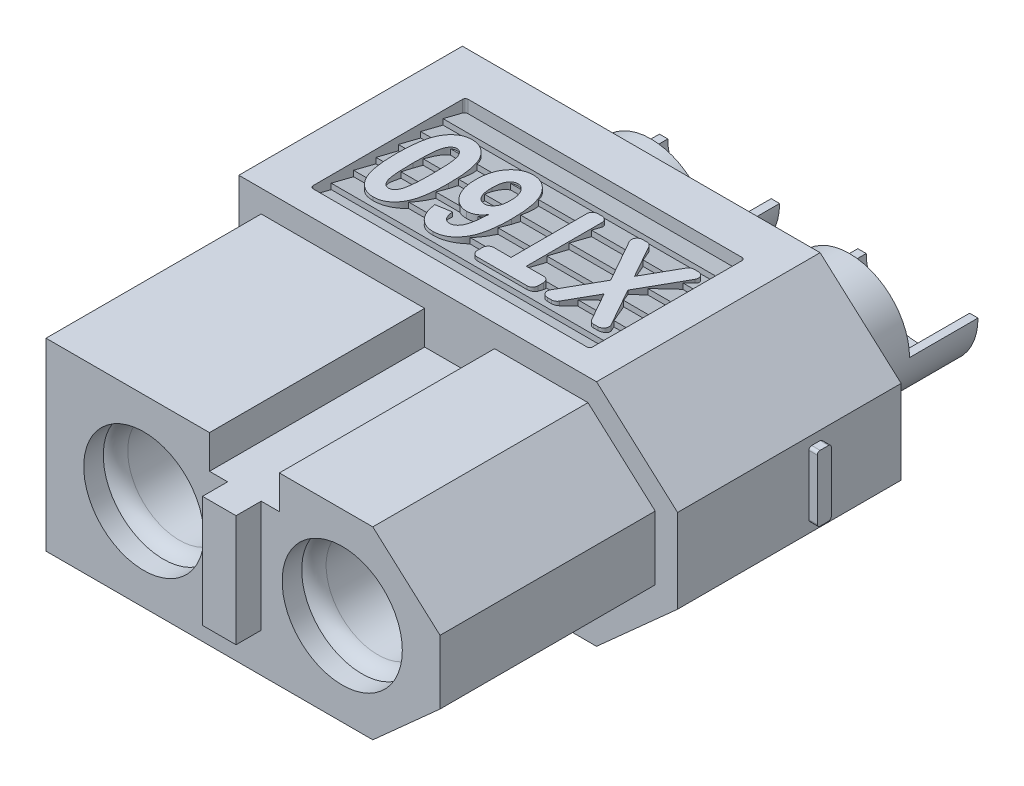
SolidWorks part; units mm, degrees
material "Nylon 101"
ref_plane "Plano frontal" through (0, 0, 0) normal (0, 0, 1) x (1, 0, 0)
ref_plane "Plano superior" through (0, 0, 0) normal (0, 1, 0) x (1, 0, 0)
ref_plane "Plano direito" through (0, 0, 0) normal (1, 0, 0) x (0, 0, -1)
sketch "Esboço1" plane through (0, 0, 0) normal (0, 0, 1) x (1, 0, 0)
  line L0 (0, 0) -> (12.8, 0)
  line L1 (12.8, 0) -> (15.7, 2.6)
  line L2 (15.7, 2.6) -> (15.7, 5.6)
  line L3 (15.7, 5.6) -> (12.8, 8.2)
  line L4 (12.8, 8.2) -> (0, 8.2)
  line L5 (0, 8.2) -> (0, 0)
  dimension "D1" = 12.8
  dimension "D2" = 3
  dimension "D3" = 15.7
  dimension "D4" = 8.2
extrude "Ressalto-extrusão1" add sketch "Esboço1" along normal blind 16.2
sketch "Esboço2" plane through (0, 0, 16.2) normal (0, 0, 1) x (1, 0, 0)
  line L0 (0.75, 7.45) -> (0.75, 0.75)
  line L1 (0.75, 0.75) -> (12.513, 0.75)
  line L2 (12.513, 0.75) -> (14.95, 2.9349)
  line L3 (14.95, 2.9349) -> (14.95, 5.2651)
  line L4 (14.95, 5.2651) -> (12.513, 7.45)
  line L5 (12.513, 7.45) -> (0.75, 7.45)
  line L6 (0, 8.2) -> (0, 0)
  line L7 (0, 0) -> (12.8, 0)
  line L8 (12.8, 0) -> (15.7, 2.6)
  line L9 (15.7, 2.6) -> (15.7, 5.6)
  line L10 (15.7, 5.6) -> (12.8, 8.2)
  line L11 (12.8, 8.2) -> (0, 8.2)
  line L12 (0, 8.2) -> (0, 0) construction
  line L13 (0, 0) -> (12.8, 0) construction
  line L14 (12.8, 0) -> (15.7, 2.6) construction
  line L15 (15.7, 2.6) -> (15.7, 5.6) construction
  line L16 (15.7, 5.6) -> (12.8, 8.2) construction
  line L17 (12.8, 8.2) -> (0, 8.2) construction
  dimension "D1" = 0
  dimension "D2" = 0.75
extrude "Corte-extrusão1" cut sketch "Esboço2" against normal blind 9.4
sketch "Esboço3" plane through (0, 0, 6.8) normal (0, 0, 1) x (1, 0, 0)
  line L1 (7.1, 1.66) -> (8.7, 1.66)
  line L2 (7.1, 1.66) -> (7.1, 0.75)
  line L3 (7.1, 0.75) -> (8.7, 0.75)
  line L4 (8.7, 1.66) -> (8.7, 0.75)
  line L7 (0.75, 0.75) -> (12.513, 0.75) construction
  line L8 (0, 0) -> (12.8, 0) construction
  line L9 (0, 8.2) -> (0, 0) construction
  dimension "D1" = 1.6
  dimension "D2" = 1.66
  dimension "D3" = 8.7
extrude "Ressalto-extrusão2" add sketch "Esboço3" along normal blind 8
sketch "Esboço4" plane through (0, 0, 6.8) normal (0, 0, 1) x (1, 0, 0)
  line L0 (12.513, 7.45) -> (0.75, 7.45) construction
  line L1 (8.7, 1.75) -> (7.1, 1.75)
  line L2 (8.7, 1.75) -> (8.7, 6.45)
  line L3 (8.7, 6.45) -> (7.1, 6.45)
  line L4 (7.1, 1.75) -> (7.1, 6.45)
  line L5 (0.75, 0.75) -> (7.1, 0.75) construction
  line L7 (7.1, 1.66) -> (7.1, 0.75) construction
  line L8 (8.7, 0.75) -> (8.7, 1.66) construction
  dimension "D1" = 1
  dimension "D2" = 1
extrude "Corte-extrusão2" cut sketch "Esboço4" against normal blind 1.5
sketch "Esboço5" plane through (0, 0, 0) normal (0, 0, -1) x (-1, 0, 0)
  line L0 (-15.7, 2.6) -> (-15.7, 5.6) construction
  line L3 (0, 8.2) -> (0, 0) construction
  circle A0 centre (-11.35, 4.1) radius 3
  circle A1 centre (-4.25, 4.1) radius 3
  point P6 (-15.7, 4.1)
  point P9 (-15.7, 4.1)
  dimension "D1" = 6
  dimension "D3" = 4.25
  dimension "D2" = 4.35
extrude "Corte-extrusão3" cut sketch "Esboço5" against normal blind 2
sketch "Esboço6" plane through (0, 0, 2) normal (0, 0, -1) x (-1, 0, 0)
  line L0 (-15.7, 2.6) -> (-15.7, 5.6) construction
  line L3 (0, 8.2) -> (0, 0) construction
  circle A0 centre (-11.35, 4.1) radius 2.15
  circle A2 centre (-4.25, 4.1) radius 2.15
  point P4 (-15.7, 4.1)
  dimension "D1" = 4.3
  dimension "D2" = 6.5
  dimension "D3" = 6.4
extrude "Corte-extrusão4" cut sketch "Esboço6" against normal through all
sketch "Esboço7" plane through (0, 0, 0) normal (-1, 0, 0) x (0, 0, 1)
  line L0 (2.8, 4.35) -> (2.05, 4.35)
  line L1 (4.25, 4.35) -> (3.5, 4.35)
  line L2 (4.35, 4.25) -> (4.35, 3.95)
  line L3 (4.25, 3.85) -> (3.5, 3.85)
  line L4 (1.95, 4.25) -> (1.95, 3.95)
  line L5 (3.3, 5.3) -> (3, 5.3)
  line L6 (3.4, 5.2) -> (3.4, 4.45)
  line L7 (3.3, 2.9) -> (3, 2.9)
  line L8 (2.9, 5.2) -> (2.9, 4.45)
  line L9 (2.8, 3.85) -> (2.05, 3.85)
  line L10 (3.4, 3.75) -> (3.4, 3)
  line L11 (2.9, 3.75) -> (2.9, 3)
  line L12 (0, 8.2) -> (0, 0) construction
  arc A0 (3, 2.9) -> (2.9, 3) centre (3, 3) cw
  arc A1 (3.3, 5.3) -> (3.4, 5.2) centre (3.3, 5.2) cw
  arc A2 (3, 5.3) -> (2.9, 5.2) centre (3, 5.2) ccw
  arc A3 (2.05, 4.35) -> (1.95, 4.25) centre (2.05, 4.25) ccw
  arc A4 (2.05, 3.85) -> (1.95, 3.95) centre (2.05, 3.95) cw
  arc A5 (2.8, 3.85) -> (2.9, 3.75) centre (2.8, 3.75) cw
  arc A6 (2.8, 4.35) -> (2.9, 4.45) centre (2.8, 4.45) ccw
  arc A7 (3.5, 3.85) -> (3.4, 3.75) centre (3.5, 3.75) ccw
  arc A8 (3.4, 3) -> (3.3, 2.9) centre (3.3, 3) cw
  arc A9 (4.35, 3.95) -> (4.25, 3.85) centre (4.25, 3.95) cw
  arc A10 (4.25, 4.35) -> (4.35, 4.25) centre (4.25, 4.25) cw
  arc A11 (3.5, 4.35) -> (3.4, 4.45) centre (3.5, 4.45) cw
  point P12 (1.95, 4.1)
  point P15 (0, 4.1)
  point P28 (2.9, 3.85)
  point P33 (3.4, 3.85)
  point P38 (4.35, 3.85)
  point P41 (4.35, 4.35)
  dimension "D4" = 0.1
  dimension "D1" = 2.4
  dimension "D2" = 0.5
  dimension "D3" = 4.35
extrude "Ressalto-extrusão3" add sketch "Esboço7" along normal blind 0.3
sketch "Esboço8" plane through (15.7, 0, 0) normal (1, 0, 0) x (0, 0, -1)
  line L0 (0, 2.6) -> (0, 5.6) construction
  line L1 (-3.2, 2.925) -> (-2.9, 2.925)
  line L2 (-3.3, 3.025) -> (-3.3, 5.175)
  line L3 (-3.2, 5.275) -> (-2.9, 5.275)
  line L4 (-2.8, 3.025) -> (-2.8, 5.175)
  arc A0 (-3.3, 5.175) -> (-3.2, 5.275) centre (-3.2, 5.175) cw
  arc A1 (-2.9, 5.275) -> (-2.8, 5.175) centre (-2.9, 5.175) cw
  arc A2 (-3.2, 2.925) -> (-3.3, 3.025) centre (-3.2, 3.025) cw
  arc A3 (-2.9, 2.925) -> (-2.8, 3.025) centre (-2.9, 3.025) ccw
  point P4 (-2.8, 4.1)
  point P7 (0, 4.1)
  point P10 (-3.3, 5.275)
  point P13 (-2.8, 5.275)
  point P18 (-2.8, 2.925)
  dimension "D4" = 0.1
  dimension "D1" = 2.35
  dimension "D2" = 0.5
  dimension "D3" = 3.3
extrude "Ressalto-extrusão4" add sketch "Esboço8" along normal blind 0.3
sketch "Esboço9" plane through (0, 0, 0) normal (0, -1, 0) x (1, 0, 0)
  line L0 (12.8, 16.2) -> (12.8, 0) construction
  line L1 (1.75, 7.0931) -> (11.55, 7.0931)
  line L2 (1.65, 6.9931) -> (1.65, 1.6431)
  line L3 (1.75, 1.5431) -> (11.55, 1.5431)
  line L4 (11.65, 6.9931) -> (11.65, 1.6431)
  arc A0 (1.65, 1.6431) -> (1.75, 1.5431) centre (1.75, 1.6431) ccw
  arc A1 (11.55, 1.5431) -> (11.65, 1.6431) centre (11.55, 1.6431) ccw
  arc A2 (11.55, 7.0931) -> (11.65, 6.9931) centre (11.55, 6.9931) cw
  arc A3 (1.75, 7.0931) -> (1.65, 6.9931) centre (1.75, 6.9931) ccw
  dimension "D1" = 0.1
  dimension "D2" = 1.15
  dimension "D3" = 10
  dimension "D4" = 5.55
extrude "Corte-extrusão5" cut sketch "Esboço9" against normal blind 0.75
sketch "Esboço10" plane through (1.65, 0, 0) normal (1, 0, 0) x (0, 0, -1)
  line L0 (-6.8, 0.75) -> (-1.6431, 0.75) construction
  line L1 (-1.5431, 0.75) -> (-1.5431, 0) construction
  line L2 (-3.1431, 0.25) -> (-2.3431, 0.45)
  line L3 (-2.3431, 0.45) -> (-2.3431, 0.25)
  line L5 (-3.1431, 0.45) -> (-3.1431, 0.25)
  line L6 (-2.3431, 0.45) -> (-2.3431, 0.25)
  line L7 (-3.9431, 0.25) -> (-3.1431, 0.45)
  line L8 (-3.9431, 0.45) -> (-3.9431, 0.25)
  line L9 (-4.7431, 0.25) -> (-3.9431, 0.45)
  line L10 (-4.7431, 0.45) -> (-4.7431, 0.25)
  line L11 (-5.5431, 0.25) -> (-4.7431, 0.45)
  line L12 (-5.5431, 0.45) -> (-5.5431, 0.25)
  line L13 (-6.3431, 0.25) -> (-5.5431, 0.45)
  line L14 (-6.3431, 0.45) -> (-6.3431, 0.25)
  line L15 (-7.1431, 0.25) -> (-6.3431, 0.45)
  line L16 (-7.1431, 0.45) -> (-7.1431, 0.25)
  line L17 (-7.1431, 0.45) -> (-7.1431, 0.75)
  line L19 (-2.3431, 0.25) -> (-1.5431, 0.45)
  line L20 (-7.1431, 0.75) -> (-1.5431, 0.75)
  line L21 (-1.5431, 0.45) -> (-1.5431, 0.75)
  line L31 (-2.3431, 0.25) -> (-1.5431, 0.45)
  dimension "D1" = 0.8
  dimension "D2" = 0.2
  dimension "D3" = 0.3
  dimension "D4" = 7
extrude "Ressalto-extrusão7" add sketch "Esboço10" along normal up to surface (10 mm away) up to face at (11.65, 0.45, 4.8145)
ref_plane "Plano1" through (0, 4.1, 0) normal (0, 1, 0) x (1, 0, 0)
mirror "Espelhar1" about plane through (0, 4.1, 0) normal (0, 1, 0) of "Corte-extrusão5", "Ressalto-extrusão7"
ref_plane "Plano2" through (0, 0.5, 0) normal (0, -1, 0) x (-1, 0, 0)
sketch "Esboço11" plane through (0, 0.5, 0) normal (0, -1, 0) x (-1, 0, 0)
  line L1 (-2.131, -7.0931) -> (-2.131, -1.5431) construction
  line L2 (-11.55, -7.0931) -> (-1.75, -7.0931) construction
  line L3 (-11.55, -1.5431) -> (-1.75, -1.5431) construction
  line L4 (-0.85, -6.1831) -> (-0.85, -2.4531) construction
  line L5 (-0.85, -2.4531) -> (-11.65, -2.4531) construction
  line L8 (-11.65, -3.1431) -> (-11.65, -2.3431) construction
  line L10 (-1.65, -6.9931) -> (-1.65, -1.6431) construction
  text T0 "<b><i>TGY</i></b>" font "Calibri" height in points 14
  point P8 (-0.85, -4.3181)
  point P9 (-2.131, -4.3181)
  dimension "D2" = 0.8
  dimension "D1" = 3.73
extrude "Ressalto-extrusão8" add sketch "Esboço11" along normal blind 0.3
ref_plane "Plano3" through (0, 7.7, 0) normal (0, 1, 0) x (1, 0, 0)
sketch "Esboço12" plane through (0, 7.7, 0) normal (0, 1, 0) x (1, 0, 0)
  line L0 (11.0942, -7.0931) -> (11.0942, -1.5431) construction
  line L1 (11.55, -7.0931) -> (1.75, -7.0931) construction
  line L3 (11.3535, -6.0681) -> (11.3535, -2.5681) construction
  line L6 (11.3535, -2.5681) -> (1.9746, -2.5681) construction
  line L7 (11.185, -2.8665) -> (10.3201, -4.3984)
  line L8 (10.3201, -4.3984) -> (11.0942, -5.7698)
  line L9 (10.92, -6.0681) -> (10.7649, -6.0681)
  line L10 (10.5908, -5.9665) -> (10.0126, -4.9431)
  line L11 (10.0126, -4.9431) -> (9.435, -5.9664)
  line L12 (9.2609, -6.0681) -> (9.1051, -6.0681)
  line L13 (8.931, -5.7698) -> (9.705, -4.3984)
  line L14 (9.705, -4.3984) -> (8.8401, -2.8665)
  line L15 (9.0143, -2.5681) -> (9.1699, -2.5681)
  line L16 (9.3441, -2.6698) -> (10.0126, -3.8543)
  line L17 (10.0126, -3.8543) -> (10.6817, -2.6698)
  line L18 (10.8559, -2.5681) -> (11.0109, -2.5681)
  line L19 (7.7626, -2.7681) -> (7.7626, -5.4772)
  line L20 (7.7626, -5.4772) -> (8.3808, -5.4772)
  line L21 (8.5808, -5.6772) -> (8.5808, -5.8681)
  line L22 (8.3808, -6.0681) -> (6.5989, -6.0681)
  line L23 (6.3989, -5.8681) -> (6.3989, -5.6772)
  line L24 (6.5989, -5.4772) -> (7.2171, -5.4772)
  line L25 (7.2171, -5.4772) -> (7.2171, -2.7681)
  line L26 (7.4171, -2.5681) -> (7.5626, -2.5681)
  line L27 (4.2171, -5.2045) -> (4.7626, -5.1136)
  line L28 (11.55, -1.5431) -> (1.75, -1.5431) construction
  arc A0 (7.2171, -2.7681) -> (7.4171, -2.5681) centre (7.4171, -2.7681) cw
  arc A1 (7.7626, -2.7681) -> (7.5626, -2.5681) centre (7.5626, -2.7681) ccw
  arc A2 (6.3989, -5.6772) -> (6.5989, -5.4772) centre (6.5989, -5.6772) cw
  arc A3 (6.5989, -6.0681) -> (6.3989, -5.8681) centre (6.5989, -5.8681) cw
  arc A4 (8.5808, -5.8681) -> (8.3808, -6.0681) centre (8.3808, -5.8681) cw
  arc A5 (8.3808, -5.4772) -> (8.5808, -5.6772) centre (8.3808, -5.6772) cw
  arc A6 (11.185, -2.8665) -> (11.0109, -2.5681) centre (11.0109, -2.7681) ccw
  arc A7 (10.6817, -2.6698) -> (10.8559, -2.5681) centre (10.8559, -2.7681) cw
  arc A8 (9.1699, -2.5681) -> (9.3441, -2.6698) centre (9.1699, -2.7681) cw
  arc A9 (8.8401, -2.8665) -> (9.0143, -2.5681) centre (9.0143, -2.7681) cw
  arc A10 (9.1051, -6.0681) -> (8.931, -5.7698) centre (9.1051, -5.8681) cw
  arc A11 (9.435, -5.9664) -> (9.2609, -6.0681) centre (9.2609, -5.8681) cw
  arc A12 (10.7649, -6.0681) -> (10.5908, -5.9665) centre (10.7649, -5.8681) cw
  arc A13 (11.0942, -5.7698) -> (10.92, -6.0681) centre (10.92, -5.8681) cw
  spline S0 degree 3 poles (4.7626, -5.1136) (4.7682, -5.1739) (4.7813, -5.2594) (4.8192, -5.3612) (4.8534, -5.4198) (4.8944, -5.4666) (4.9618, -5.511) (5.022, -5.5233) (5.0623, -5.5227) knots 0 0 0 0 0.323351 0.457032 0.575726 0.682828 0.785622 1 1 1 1
  spline S1 degree 3 poles (5.0623, -5.5227) (5.09, -5.5233) (5.1312, -5.5165) (5.1832, -5.4965) (5.2201, -5.4751) (5.2548, -5.4474) (5.2873, -5.4137) (5.3188, -5.3744) (5.3485, -5.328) (5.3759, -5.2719) (5.4005, -5.2044) (5.4208, -5.1242) (5.4414, -5.0325) (5.4567, -4.9277) (5.4769, -4.7639) (5.4853, -4.6343) (5.4898, -4.544) knots 0 0 0 0 0.071106 0.106432 0.143035 0.180361 0.220458 0.263402 0.309744 0.362096 0.423824 0.494518 0.575001 0.665718 0.767055 1 1 1 1
  spline S2 degree 3 poles (5.4898, -4.544) (5.4583, -4.5903) (5.407, -4.6546) (5.3276, -4.7255) (5.2671, -4.7681) (5.2028, -4.8002) (5.1126, -4.8326) (5.0401, -4.8399) (4.992, -4.8409) knots 0 0 0 0 0.277998 0.405178 0.526602 0.643637 0.760549 1 1 1 1
  spline S3 degree 3 poles (4.992, -4.8409) (4.9384, -4.84) (4.8576, -4.8324) (4.7559, -4.798) (4.6823, -4.7636) (4.6106, -4.7202) (4.5426, -4.6656) (4.4769, -4.602) (4.4148, -4.529) (4.3577, -4.4481) (4.3074, -4.36) (4.2661, -4.2652) (4.2305, -4.1646) (4.205, -4.0571) (4.1787, -3.9021) (4.1709, -3.7817) (4.1717, -3.6995) knots 0 0 0 0 0.103373 0.154207 0.205955 0.259297 0.315055 0.373347 0.435039 0.499095 0.563542 0.6298 0.697776 0.768574 0.842016 1 1 1 1
  spline S4 degree 3 poles (4.1717, -3.6995) (4.1719, -3.6124) (4.1791, -3.4851) (4.2059, -3.3214) (4.2344, -3.2096) (4.2696, -3.1044) (4.3147, -3.0075) (4.3663, -2.9169) (4.427, -2.8357) (4.4929, -2.7625) (4.5632, -2.698) (4.638, -2.6441) (4.7161, -2.5992) (4.7984, -2.5649) (4.9149, -2.5326) (5.0059, -2.5223) (5.0673, -2.5227) knots 0 0 0 0 0.157847 0.230497 0.300424 0.366636 0.431332 0.493809 0.555163 0.614703 0.672107 0.727719 0.78152 0.834986 0.88891 1 1 1 1
  spline S5 degree 3 poles (5.0673, -2.5227) (5.1348, -2.5224) (5.235, -2.5352) (5.3621, -2.5775) (5.4516, -2.6225) (5.5367, -2.6804) (5.6167, -2.7511) (5.6923, -2.8344) (5.764, -2.9301) (5.8292, -3.0408) (5.8839, -3.1688) (5.9316, -3.3125) (5.969, -3.4733) (5.9997, -3.6502) (6.0283, -3.9192) (6.0353, -4.1298) (6.0353, -4.2755) knots 0 0 0 0 0.090693 0.134685 0.17953 0.224913 0.272738 0.32276 0.375986 0.433204 0.49507 0.562819 0.636478 0.716918 0.804031 1 1 1 1
  spline S6 degree 3 poles (6.0353, -4.2755) (6.0353, -4.4236) (6.0286, -4.6379) (5.9972, -4.9112) (5.9666, -5.0917) (5.9263, -5.2555) (5.8779, -5.4031) (5.8201, -5.5343) (5.7518, -5.6479) (5.6774, -5.7469) (5.5976, -5.8325) (5.5132, -5.906) (5.4224, -5.9645) (5.3276, -6.0115) (5.1918, -6.0556) (5.0843, -6.0686) (5.0119, -6.0681) knots 0 0 0 0 0.192658 0.278521 0.357597 0.430563 0.497753 0.559502 0.616537 0.669747 0.720292 0.768555 0.814847 0.860431 0.905809 1 1 1 1
  spline S7 degree 3 poles (5.0119, -6.0681) (4.9619, -6.0679) (4.888, -6.0616) (4.793, -6.0396) (4.7258, -6.0161) (4.6619, -5.9851) (4.6002, -5.9489) (4.5418, -5.9054) (4.4872, -5.8546) (4.4355, -5.7981) (4.3903, -5.7331) (4.3488, -5.6621) (4.3131, -5.5835) (4.2805, -5.4988) (4.2454, -5.3724) (4.226, -5.2732) (4.2171, -5.2045) knots 0 0 0 0 0.115543 0.170649 0.225187 0.279791 0.334526 0.390474 0.447811 0.50673 0.567186 0.630471 0.696846 0.766493 0.839959 1 1 1 1
  spline S8 degree 3 poles (5.4444, -3.7215) (5.4434, -3.6718) (5.4418, -3.5989) (5.429, -3.5058) (5.4165, -3.4425) (5.399, -3.3843) (5.3797, -3.33) (5.3555, -3.2808) (5.3274, -3.2367) (5.298, -3.1971) (5.2668, -3.1628) (5.2343, -3.1343) (5.2019, -3.1095) (5.1674, -3.0908) (5.1199, -3.0739) (5.0828, -3.0683) (5.058, -3.0681) knots 0 0 0 0 0.178482 0.260709 0.336948 0.409468 0.478213 0.543503 0.605673 0.665087 0.720356 0.771459 0.82001 0.866345 0.91145 1 1 1 1
  spline S9 degree 3 poles (5.058, -3.0681) (5.0113, -3.0673) (4.9398, -3.0858) (4.8626, -3.147) (4.82, -3.1972) (4.7904, -3.2464) (4.7705, -3.2897) (4.7544, -3.3389) (4.7402, -3.3931) (4.7296, -3.4532) (4.7205, -3.5442) (4.7163, -3.6154) (4.7171, -3.6647) knots 0 0 0 0 0.182718 0.277312 0.381921 0.439334 0.501577 0.568146 0.641921 0.72105 0.806868 1 1 1 1
  spline S10 degree 3 poles (4.7171, -3.6647) (4.717, -3.7159) (4.7193, -3.7901) (4.7313, -3.8847) (4.7423, -3.9476) (4.7573, -4.005) (4.7747, -4.0573) (4.7959, -4.1039) (4.8285, -4.1562) (4.8734, -4.2114) (4.9574, -4.2751) (5.0328, -4.2967) (5.0829, -4.2954) knots 0 0 0 0 0.189208 0.273855 0.352112 0.425324 0.492836 0.555472 0.613995 0.720194 0.816437 1 1 1 1
  spline S11 degree 3 poles (5.0829, -4.2954) (5.1315, -4.2955) (5.2057, -4.2763) (5.2877, -4.2147) (5.333, -4.163) (5.3652, -4.1135) (5.3866, -4.0705) (5.4042, -4.0231) (5.4192, -3.9714) (5.4302, -3.915) (5.4422, -3.8316) (5.4445, -3.7663) (5.4444, -3.7215) knots 0 0 0 0 0.192976 0.293261 0.403879 0.464413 0.527516 0.593907 0.665362 0.741186 0.821937 1 1 1 1
  spline S12 degree 3 poles (2.8776, -6.0681) (2.8107, -6.0678) (2.7113, -6.0563) (2.586, -6.0147) (2.4983, -5.9711) (2.4159, -5.915) (2.3386, -5.8466) (2.2662, -5.766) (2.1985, -5.6725) (2.1376, -5.5631) (2.0855, -5.436) (2.0419, -5.2906) (2.0063, -5.1269) (1.978, -4.9448) (1.9513, -4.6654) (1.9446, -4.4461) (1.9444, -4.294) knots 0 0 0 0 0.08972 0.132871 0.17644 0.220536 0.26618 0.314488 0.365396 0.420661 0.481834 0.549191 0.623951 0.706175 0.796104 1 1 1 1
  spline S13 degree 3 poles (1.9444, -4.294) (1.9446, -4.1424) (1.9512, -3.9238) (1.9781, -3.6451) (2.0061, -3.4634) (2.0421, -3.2998) (2.0852, -3.1545) (2.1378, -3.0275) (2.1984, -2.9183) (2.2663, -2.8251) (2.3378, -2.744) (2.4152, -2.6758) (2.4975, -2.6199) (2.5847, -2.5759) (2.7095, -2.5348) (2.8083, -2.5226) (2.8748, -2.5227) knots 0 0 0 0 0.203744 0.29357 0.37599 0.450617 0.518438 0.579462 0.634858 0.685888 0.734097 0.77985 0.824051 0.867439 0.910692 1 1 1 1
  spline S14 degree 3 poles (2.8748, -2.5227) (2.9415, -2.5237) (3.0413, -2.5333) (3.1662, -2.5756) (3.2543, -2.618) (3.3363, -2.6745) (3.4139, -2.742) (3.4862, -2.8219) (3.5413, -2.8978) (3.5827, -2.965) (3.6116, -3.0212) (3.6385, -3.082) (3.6644, -3.1471) (3.6866, -3.2179) (3.708, -3.2929) (3.7271, -3.3725) (3.744, -3.4569) (3.76, -3.5458) (3.7721, -3.64) (3.784, -3.7384) (3.792, -3.842) (3.7994, -3.9499) (3.8057, -4.1036) (3.809, -4.221) (3.808, -4.3011) knots 0 0 0 0 0.089418 0.132451 0.175762 0.219738 0.26505 0.312991 0.363505 0.390209 0.418376 0.447842 0.479108 0.512034 0.546898 0.583358 0.621467 0.661946 0.704107 0.748387 0.794432 0.842956 0.893008 1 1 1 1
  spline S15 degree 3 poles (3.808, -4.3011) (3.8078, -4.4522) (3.8011, -4.6701) (3.7744, -4.9476) (3.7461, -5.1285) (3.7104, -5.2915) (3.6671, -5.4365) (3.6147, -5.5633) (3.554, -5.6725) (3.4861, -5.7657) (3.4146, -5.8468) (3.3372, -5.915) (3.255, -5.9709) (3.1677, -6.0149) (3.0429, -6.056) (2.9441, -6.0682) (2.8776, -6.0681) knots 0 0 0 0 0.203492 0.293171 0.375116 0.449884 0.517528 0.578668 0.634169 0.685295 0.733595 0.779434 0.823719 0.867188 0.910523 1 1 1 1
  spline S16 degree 3 poles (2.8762, -5.5227) (2.9014, -5.5225) (2.9391, -5.5157) (2.9853, -5.4936) (3.0177, -5.4696) (3.0472, -5.4386) (3.0753, -5.4017) (3.1015, -5.3582) (3.1264, -5.3061) (3.1493, -5.2412) (3.1662, -5.1592) (3.1829, -5.0598) (3.1947, -4.9418) (3.2056, -4.806) (3.2148, -4.5879) (3.2172, -4.4152) (3.2171, -4.294) knots 0 0 0 0 0.054972 0.082543 0.111449 0.142586 0.175843 0.2128 0.253578 0.301908 0.362982 0.436475 0.522453 0.622213 0.734739 1 1 1 1
  spline S17 degree 3 poles (3.2171, -4.294) (3.2172, -4.173) (3.2148, -4.0006) (3.2056, -3.7827) (3.1946, -3.6468) (3.1829, -3.5291) (3.1662, -3.4301) (3.1492, -3.3487) (3.1266, -3.2841) (3.1014, -3.2324) (3.0751, -3.189) (3.0477, -3.1515) (3.0174, -3.1212) (2.9854, -3.0972) (2.9391, -3.0752) (2.9014, -3.0683) (2.8762, -3.0681) knots 0 0 0 0 0.265262 0.378009 0.477964 0.564111 0.637236 0.697923 0.746348 0.786738 0.823768 0.857504 0.888332 0.917295 0.944921 1 1 1 1
  spline S18 degree 3 poles (2.8762, -3.0681) (2.8509, -3.0683) (2.8128, -3.0749) (2.7663, -3.0974) (2.7333, -3.1209) (2.7037, -3.1525) (2.675, -3.1892) (2.6497, -3.2336) (2.6244, -3.2852) (2.6028, -3.3503) (2.5854, -3.4315) (2.5689, -3.5305) (2.5569, -3.648) (2.5471, -3.7837) (2.5374, -4.001) (2.5353, -4.1732) (2.5353, -4.294) knots 0 0 0 0 0.055564 0.083174 0.11254 0.143719 0.17775 0.214492 0.255326 0.303553 0.364206 0.437289 0.523386 0.622727 0.735409 1 1 1 1
  spline S19 degree 3 poles (2.5353, -4.294) (2.5354, -4.4152) (2.5374, -4.5879) (2.5471, -4.8059) (2.5568, -4.9419) (2.5689, -5.0598) (2.5854, -5.1593) (2.6027, -5.241) (2.6243, -5.3063) (2.6498, -5.3579) (2.6747, -5.4022) (2.7039, -5.4384) (2.7333, -5.4699) (2.7663, -5.4934) (2.8128, -5.5158) (2.8509, -5.5225) (2.8762, -5.5227) knots 0 0 0 0 0.265055 0.377494 0.477137 0.563048 0.636484 0.697511 0.745634 0.78638 0.823042 0.856591 0.887703 0.917006 0.944556 1 1 1 1
  point P7 (11.0942, -4.3181)
  point P10 (11.3535, -4.3181)
  dimension "D2" = 0.2
  dimension "D1" = 3.5
extrude "Ressalto-extrusão9" add sketch "Esboço12" along normal blind 0.3
sketch "Sketch2" plane through (0, 8.2, 0) normal (0, 1, 0) x (1, 0, 0)
  line L0 (0, -8) -> (15.7, -8)
  line L4 (0, -8) -> (-5.5548, -17.5412)
  line L5 (-5.5548, -17.5412) -> (20.2592, -17.784)
  line L6 (20.2592, -17.784) -> (15.7, -8)
  dimension "D1" = 8
extrude "Cut-Extrude1" cut sketch "Sketch2" against normal blind 10
sketch "Sketch3" plane through (0, 0, 6.8) normal (0, 0, 1) x (1, 0, 0)
  line L10 (0.75, 0.75) -> (7.1, 0.75)
  line L11 (7.1, 0.75) -> (7.1, 1.66)
  line L12 (7.1, 1.66) -> (8.7, 1.66)
  line L13 (8.7, 1.66) -> (8.7, 0.75)
  line L14 (8.7, 0.75) -> (12.513, 0.75)
  line L15 (12.513, 0.75) -> (14.95, 2.9349)
  line L16 (14.95, 2.9349) -> (14.95, 5.2651)
  line L17 (14.95, 5.2651) -> (12.513, 7.45)
  line L18 (12.513, 7.45) -> (0.75, 7.45)
  line L19 (0.75, 7.45) -> (0.75, 0.75)
  line L20 (0.75, 0.75) -> (7.1, 0.75)
  line L21 (7.1, 0.75) -> (7.1, 1.66)
  line L22 (7.1, 1.66) -> (8.7, 1.66)
  line L23 (8.7, 1.66) -> (8.7, 0.75)
  line L24 (8.7, 0.75) -> (12.513, 0.75)
  line L25 (12.513, 0.75) -> (14.95, 2.9349)
  line L26 (14.95, 2.9349) -> (14.95, 5.2651)
  line L27 (14.95, 5.2651) -> (12.513, 7.45)
  line L28 (12.513, 7.45) -> (0.75, 7.45)
  line L29 (0.75, 7.45) -> (0.75, 0.75)
  dimension "D1" = 0
extrude "Boss-Extrude1" add sketch "Sketch3" along normal up to surface (1.2 mm away) up to face at (8.8026, 2.942, 8)
sketch "Sketch4" plane through (0, 0, 2) normal (0, 0, -1) x (-1, 0, 0)
  circle A0 centre (-11.35, 4.1) radius 3 construction
  circle A1 centre (-4.25, 4.1) radius 3 construction
  circle A2 centre (-11.35, 4.1) radius 3
  circle A3 centre (-4.25, 4.1) radius 3
extrude "Boss-Extrude2" add sketch "Sketch4" along normal up to surface (2 mm away) up to face at (1.25, 4.1, 0)
sketch "Sketch5" plane through (0, 0, 8) normal (0, 0, 1) x (1, 0, 0)
  line L27 (14.9, 5.2428) -> (12.4939, 7.4)
  line L28 (14.9, 2.9572) -> (14.9, 5.2428)
  line L29 (12.4939, 0.8) -> (14.9, 2.9572)
  line L30 (0.8, 0.8) -> (12.4939, 0.8)
  line L31 (0.8, 7.4) -> (0.8, 0.8)
  line L32 (12.4939, 7.4) -> (0.8, 7.4)
  line L33 (14.9, 5.2428) -> (12.4939, 7.4)
  line L34 (14.9, 2.9572) -> (14.9, 5.2428)
  line L35 (12.4939, 0.8) -> (14.9, 2.9572)
  line L36 (0.8, 0.8) -> (12.4939, 0.8)
  line L37 (0.8, 7.4) -> (0.8, 0.8)
  line L38 (12.4939, 7.4) -> (0.8, 7.4)
  dimension "D1" = 0.8
extrude "Boss-Extrude3" add sketch "Sketch5" along normal blind 7.7
sketch "Sketch6" plane through (0, 0, 15.7) normal (0, 0, 1) x (1, 0, 0)
  line L0 (14.9, 2.9572) -> (14.9, 5.2428) construction
  line L1 (0.8, 7.4) -> (0.8, 0.8) construction
  line L2 (14.9, 4.1) -> (0.8, 4.1) construction
  circle A0 centre (4.3, 4.1) radius 2.15
  circle A1 centre (11.4, 4.1) radius 2.15
  dimension "D1" = 4.3
  dimension "D2" = 4.3
  dimension "D4" = 3.5
  dimension "D3" = 7.1
extrude "Cut-Extrude2" cut sketch "Sketch6" against normal blind 0.7
sketch "Sketch7" plane through (0, 0, 15) normal (0, 0, 1) x (1, 0, 0)
  circle A0 centre (4.3, 4.1) radius 1.85
  circle A1 centre (11.4, 4.1) radius 1.85
  dimension "D1" = 3.7
  dimension "D2" = 3.7
extrude "Cut-Extrude3" cut sketch "Sketch7" against normal blind 10.65
sketch "Sketch8" plane through (0, 0, 15) normal (0, 0, 1) x (1, 0, 0)
  circle A0 centre (4.3, 4.1) radius 1.85 construction
  circle A1 centre (4.3, 4.1) radius 2.15
  circle A2 centre (4.3, 4.1) radius 2.15
  circle A3 centre (11.4, 4.1) radius 2.15
  circle A4 centre (11.4, 4.1) radius 2.15
  circle A5 centre (11.4, 4.1) radius 1.85 construction
  circle A6 centre (4.3, 4.1) radius 1.85
  circle A7 centre (11.4, 4.1) radius 1.85
  dimension "D1" = 0
  dimension "D2" = 0
extrude "Boss-Extrude4" add sketch "Sketch8" against normal blind 19.9
chamfer "Chamfer1" distance 1 angle 60 2 edges at (9.55, 4.1, 2) (2.45, 4.1, 2)
sketch "Sketch9" plane through (0, 0, 15.7) normal (0, 0, 1) x (1, 0, 0)
  line L1 (7.3, 6.2) -> (8.5, 6.2)
  line L2 (7.3, 6.2) -> (7.3, 2.2)
  line L3 (7.3, 2.2) -> (8.5, 2.2)
  line L4 (8.5, 6.2) -> (8.5, 2.2)
  line L5 (7.3, 6.2) -> (8.5, 2.2) construction
  line L6 (7.3, 2.2) -> (8.5, 6.2) construction
  line L7 (14.9, 2.9572) -> (14.9, 5.2428) construction
  line L8 (12.4939, 7.4) -> (0.8, 7.4) construction
  point P0 (7.9, 4.2)
  dimension "D1" = 4
  dimension "D2" = 1.2
  dimension "D3" = 1.2
  dimension "D4" = 6.4
extrude "Boss-Extrude5" add sketch "Sketch9" along normal blind 0.9
sketch "Sketch10" plane through (0, 0, 15.7) normal (0, 0, 1) x (1, 0, 0)
  line L0 (0.8, 0.8) -> (12.4939, 0.8) construction
  line L3 (6.65, 0.8) -> (9.15, 0.8)
  line L5 (6.65, 2) -> (9.15, 0.8) construction
  line L6 (6.65, 0.8) -> (9.15, 2) construction
  line L7 (7.9, 6.2) -> (7.9, -2.453) construction
  line L8 (8.5, 6.2) -> (7.3, 6.2) construction
  line L9 (0.8, 4.1) -> (14.9, 4.1) construction
  line L10 (0.8, 7.4) -> (0.8, 0.8) construction
  line L11 (14.9, 2.9572) -> (14.9, 5.2428) construction
  line L12 (6.65, 7.4) -> (9.15, 7.4)
  line L13 (9.15, 6.2) -> (9.15, 7.4)
  line L14 (6.65, 6.2) -> (9.15, 6.2)
  line L15 (6.65, 6.2) -> (6.65, 7.4)
  point P0 (7.9, 1.4)
  line M10 (12.4939, 7.4) -> (0.8, 7.4)
  dimension "D1" = 1.2
extrude "Cut-Extrude4" cut sketch "Sketch10" against normal up to surface (7.7 mm away) contours L15 L14 L13 M10 up to face at (9.5, 4.1, 8)
fillet "Fillet2" radius 0.7 2 edges at (13.25, 4.1, 15) (6.15, 4.1, 15)
sketch "Sketch11" plane through (0, 0, 0) normal (-1, 0, 0) x (0, 0, 1)
  line L0 (-4.9, 4.1) -> (-2.45, 4.1)
  line L1 (-4.9, 6.25) -> (-4.9, 1.95) construction
  line L2 (-2.45, 4.1) -> (-2.45, 6.1)
  line L3 (-4.9, 13.0049) -> (-2.45, 13.0049)
  line L4 (-4.9, 6.1) -> (0, 6.1) construction
  line L5 (0, 8.2) -> (0, 0) construction
  line L6 (-4.9, 4.1) -> (-4.9, 13.0049)
  line L7 (-2.45, 13.0049) -> (-2.45, 5.9164)
extrude "Cut-Extrude5" cut sketch "Sketch11" against normal blind 16.9 contours L4 L6 L0 L2 | L6 L4 L7 L3
sketch "Sketch12" plane through (0, 0, 0) normal (0, 0, -1) x (-1, 0, 0)
  line L0 (0, 8.2) -> (0, 0) construction
  circle A0 centre (-11.4, 4.1) radius 3
  circle A1 centre (-4.3, 4.1) radius 3
  circle A2 centre (-11.4, 4.1) radius 2.15
  circle A3 centre (-4.3, 4.1) radius 2.15
  point P6 (0, 4.1)
  dimension "D1" = 6
  dimension "D2" = 6
  dimension "D3" = 7.1
  dimension "D4" = 4.3
extrude "Cut-Extrude7" cut sketch "Sketch12" against normal blind 1
chamfer "Chamfer3" distance 1.7 angle 20 2 edges at (6.15, 4.1, 0) (13.25, 4.1, 0)
